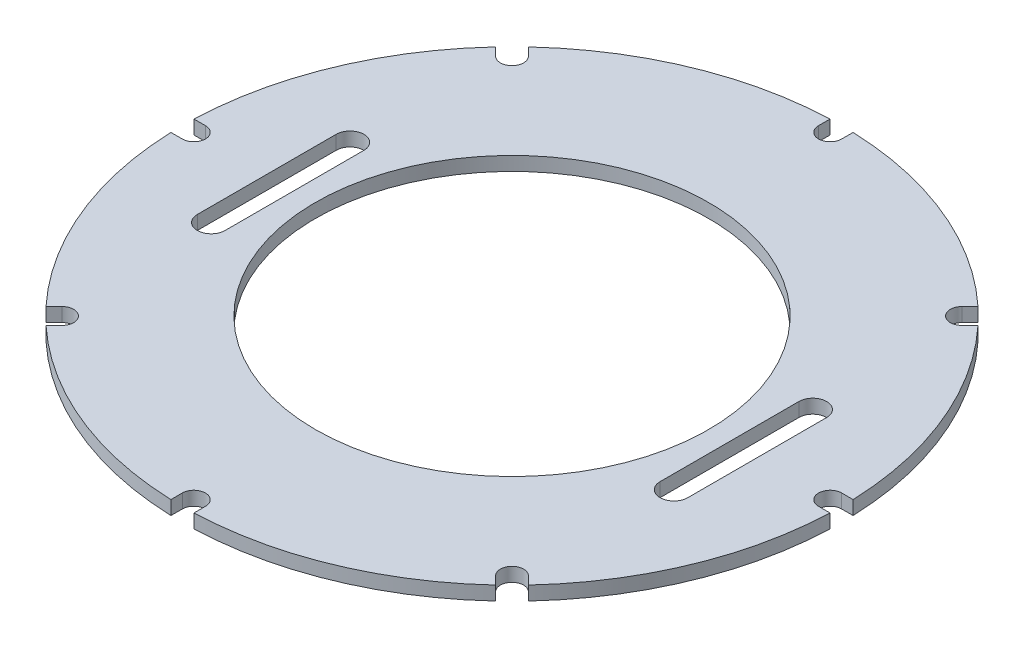
SolidWorks part; units mm, degrees
ref_plane "Front Plane" through (0, 0, 0) normal (0, 0, 1) x (1, 0, 0)
ref_plane "Top Plane" through (0, 0, 0) normal (0, 1, 0) x (1, 0, 0)
ref_plane "Right Plane" through (0, 0, 0) normal (1, 0, 0) x (0, 0, -1)
sketch "Sketch1" plane through (0, 0, 0) normal (0, 1, 0) x (1, 0, 0)
  line L0 (10, -3) -> (10, 3) construction
  line L1 (9.4, -3) -> (9.4, 3)
  line L2 (10.6, -3) -> (10.6, 3)
  line L3 (0, 0) -> (0, -14.25) construction
  line L4 (-10, -3) -> (-10, 3) construction
  line L5 (-9.4, -3) -> (-9.4, 3)
  line L6 (-10.6, -3) -> (-10.6, 3)
  line L7 (-0.5, -13.75) -> (-0.5, -14.2412)
  line L8 (0.5, -13.75) -> (0.5, -14.2412)
  line L9 (-10.0763, -9.3692) -> (-10.4236, -9.7165)
  line L10 (-9.3692, -10.0763) -> (-9.7165, -10.4236)
  line L11 (-13.75, 0.5) -> (-14.2412, 0.5)
  line L12 (-13.75, -0.5) -> (-14.2412, -0.5)
  line L13 (-9.3692, 10.0763) -> (-9.7165, 10.4236)
  line L14 (-10.0763, 9.3692) -> (-10.4236, 9.7165)
  line L15 (0.5, 13.75) -> (0.5, 14.2412)
  line L16 (-0.5, 13.75) -> (-0.5, 14.2412)
  line L17 (10.0763, 9.3692) -> (10.4236, 9.7165)
  line L18 (9.3692, 10.0763) -> (9.7165, 10.4236)
  line L19 (13.75, -0.5) -> (14.2412, -0.5)
  line L20 (13.75, 0.5) -> (14.2412, 0.5)
  line L21 (9.3692, -10.0763) -> (9.7165, -10.4236)
  line L22 (10.0763, -9.3692) -> (10.4236, -9.7165)
  circle A0 centre (0, 0) radius 14.25
  circle A1 centre (0, 0) radius 8.5
  arc A2 (9.4, -3) -> (10.6, -3) centre (10, -3) ccw
  arc A3 (10.6, 3) -> (9.4, 3) centre (10, 3) ccw
  arc A4 (-9.4, -3) -> (-10.6, -3) centre (-10, -3) cw
  arc A5 (-10.6, 3) -> (-9.4, 3) centre (-10, 3) cw
  arc A6 (0.5, -13.75) -> (-0.5, -13.75) centre (0, -13.75) ccw
  arc A7 (-9.3692, -10.0763) -> (-10.0763, -9.3692) centre (-9.7227, -9.7227) ccw
  arc A8 (-13.75, -0.5) -> (-13.75, 0.5) centre (-13.75, 0) ccw
  arc A9 (-10.0763, 9.3692) -> (-9.3692, 10.0763) centre (-9.7227, 9.7227) ccw
  arc A10 (-0.5, 13.75) -> (0.5, 13.75) centre (0, 13.75) ccw
  arc A11 (9.3692, 10.0763) -> (10.0763, 9.3692) centre (9.7227, 9.7227) ccw
  arc A12 (13.75, 0.5) -> (13.75, -0.5) centre (13.75, 0) ccw
  arc A13 (10.0763, -9.3692) -> (9.3692, -10.0763) centre (9.7227, -9.7227) ccw
  point P6 (10, 0)
  point P13 (-10, 0)
  point P61 (0, 0)
  dimension "D1" = 28.5
  dimension "D2" = 17
  dimension "D6" = 8
  dimension "D3" = 1.2
  dimension "D4" = 6
  dimension "D5" = 10
extrude "Boss-Extrude1" add sketch "Sketch1" along normal blind 0.6 contours A13 L22 A0 L19 A12 L20 L17 A11 L18 L15 A10 L16 L13 A9 L14 L11 A8 L12 L9 A7 L10 L7 A6 L8 L21 A3 L2 A2 L1 A1 L6 A5 L5 A4 region at (-0.9028, 0, 13.9956)
ref_plane "Plane1" through (0, 0.3, 0) normal (0, 1, 0) x (1, 0, 0)
sketch "Sketch2" plane through (0, 0.3, 0) normal (0, 1, 0) x (1, 0, 0)
  point P4 (13.75, 0)
  point P5 (9.7227, -9.7227)
  point P8 (0, -13.75)
  point P9 (-9.7227, -9.7227)
  point P10 (-13.75, 0)
  point P11 (-9.7227, 9.7227)
  point P12 (0, 13.75)
  point P13 (9.7227, 9.7227)
  point P14 (0, 0)
  dimension "D1" = 8
ref_plane "Plane4" through (0, 0, 0) normal (-0.7071, 0, -0.7071) x (-0.7071, 0, 0.7071)
ref_plane "Plane5" through (0, 0, 0) normal (0.7071, 0, -0.7071) x (-0.7071, 0, -0.7071)
ref_point "Point1"
ref_point "Point2"
